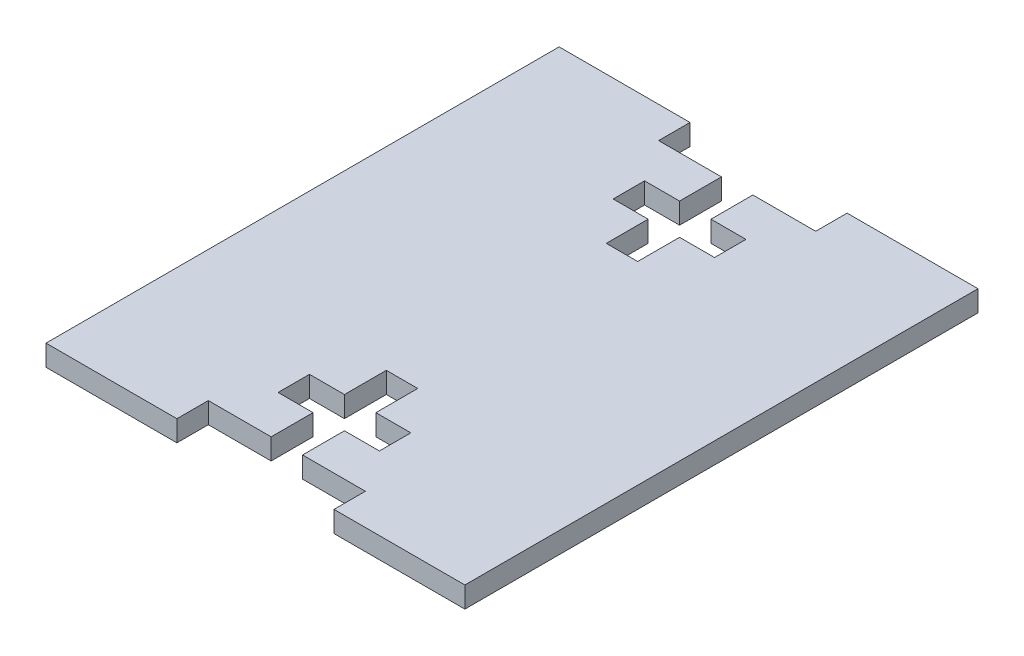
SolidWorks part; units mm, degrees
material "PVC rigido"
ref_plane "Piano frontale" through (0, 0, 0) normal (0, 0, 1) x (1, 0, 0)
ref_plane "Piano superiore" through (0, 0, 0) normal (0, 1, 0) x (1, 0, 0)
ref_plane "Piano destro" through (0, 0, 0) normal (1, 0, 0) x (0, 0, -1)
sketch "Schizzo1" plane through (0, 0, 0) normal (0, 1, 0) x (1, 0, 0)
  line L1 (-54.5649, -28.2811) -> (-14.5649, -28.2811)
  line L2 (-54.5649, -28.2811) -> (-54.5649, 20.7189)
  line L3 (-54.5649, 20.7189) -> (-14.5649, 20.7189)
  line L4 (-14.5649, -28.2811) -> (-14.5649, 20.7189)
  dimension "D1" = 40
  dimension "D2" = 49
sketch "Schizzo2" plane through (0, 0, 0) normal (0, 1, 0) x (1, 0, 0)
  line L0 (-54.5649, -3.7811) -> (-14.5649, -3.7811) construction
  line L5 (-54.5649, -28.2811) -> (-54.5649, 20.7189) construction
  line L6 (-14.5649, -28.2811) -> (-14.5649, 20.7189) construction
  line L7 (-34.5649, -28.2811) -> (-34.5649, 20.7189) construction
  line L8 (-54.5649, -28.2811) -> (-14.5649, -28.2811) construction
  line L9 (-54.5649, 20.7189) -> (-14.5649, 20.7189) construction
  line L22 (-42.0649, -28.2811) -> (-27.0649, -28.2811)
  line L23 (-42.0649, -28.2811) -> (-42.0649, -25.2811)
  line L24 (-42.0649, -25.2811) -> (-27.0649, -25.2811)
  line L25 (-27.0649, -28.2811) -> (-27.0649, -25.2811)
  line L26 (-42.0649, 20.7189) -> (-42.0649, 17.7189)
  line L27 (-42.0649, 17.7189) -> (-27.0649, 17.7189)
  line L28 (-27.0649, 20.7189) -> (-27.0649, 17.7189)
  line L29 (-42.0649, 20.7189) -> (-27.0649, 20.7189)
  point P33 (-34.5649, -25.2811)
  dimension "D3" = 15
  dimension "D4" = 3
extrude "Estrusione-Estrusione2" add sketch "Schizzo1" against normal blind 2
extrude "Taglio-Estrusione1" cut sketch "Schizzo2" against normal through all
sketch "Schizzo3" plane through (0, 0, 0) normal (0, 1, 0) x (1, 0, 0)
  line L1 (-36.0649, -25.2811) -> (-33.0649, -25.2811)
  line L2 (-54.5649, -3.7811) -> (-14.5649, -3.7811) construction
  line L3 (-54.5649, 20.7189) -> (-54.5649, -28.2811) construction
  line L15 (-14.5649, -28.2811) -> (-14.5649, 20.7189) construction
  line L19 (-34.5649, 17.7189) -> (-34.5649, -25.2811) construction
  line L20 (-42.0649, 17.7189) -> (-27.0649, 17.7189) construction
  line L21 (-27.0649, -25.2811) -> (-42.0649, -25.2811) construction
  line L26 (-36.0649, -25.2811) -> (-36.0649, -21.2811)
  line L27 (-36.0649, -21.2811) -> (-39.4049, -21.2811)
  line L28 (-39.4049, -21.2811) -> (-39.4049, -18.2811)
  line L29 (-39.4049, -18.2811) -> (-36.0649, -18.2811)
  line L30 (-36.0649, -18.2811) -> (-36.0649, -14.2811)
  line L31 (-36.0649, -14.2811) -> (-33.0649, -14.2811)
  line L32 (-33.0649, -14.2811) -> (-33.0649, -18.2811)
  line L33 (-33.0649, -18.2811) -> (-29.7249, -18.2811)
  line L34 (-29.7249, -18.2811) -> (-29.7249, -21.2811)
  line L35 (-29.7249, -21.2811) -> (-33.0649, -21.2811)
  line L36 (-33.0649, -21.2811) -> (-33.0649, -25.2811)
  line L60 (-36.0649, 6.7189) -> (-33.0649, 6.7189)
  line L61 (-36.0649, 10.7189) -> (-36.0649, 6.7189)
  line L62 (-39.4049, 10.7189) -> (-36.0649, 10.7189)
  line L63 (-39.4049, 13.7189) -> (-39.4049, 10.7189)
  line L64 (-36.0649, 13.7189) -> (-39.4049, 13.7189)
  line L65 (-36.0649, 17.7189) -> (-36.0649, 13.7189)
  line L66 (-36.0649, 17.7189) -> (-33.0649, 17.7189)
  line L67 (-33.0649, 13.7189) -> (-33.0649, 17.7189)
  line L68 (-29.7249, 13.7189) -> (-33.0649, 13.7189)
  line L69 (-29.7249, 10.7189) -> (-29.7249, 13.7189)
  line L70 (-33.0649, 10.7189) -> (-29.7249, 10.7189)
  line L71 (-33.0649, 6.7189) -> (-33.0649, 10.7189)
  point P53 (-34.5649, -25.2811)
  dimension "D8" = 3
  dimension "D9" = 4
  dimension "D10" = 4
  dimension "D11" = 3
  dimension "D12" = 3.34
extrude "Taglio-Estrusione3" cut sketch "Schizzo3" against normal through all
equation "\"Thickness2\"=2"
equation "\"Thickness3\"=3"
equation "\"D4@Schizzo2\"=\"Thickness3\""
equation "\"D1@Estrusione-Estrusione2\"=\"Thickness2\""
equation "\"D2@Schizzo1\"=\"Thickness2\"*2+45"
